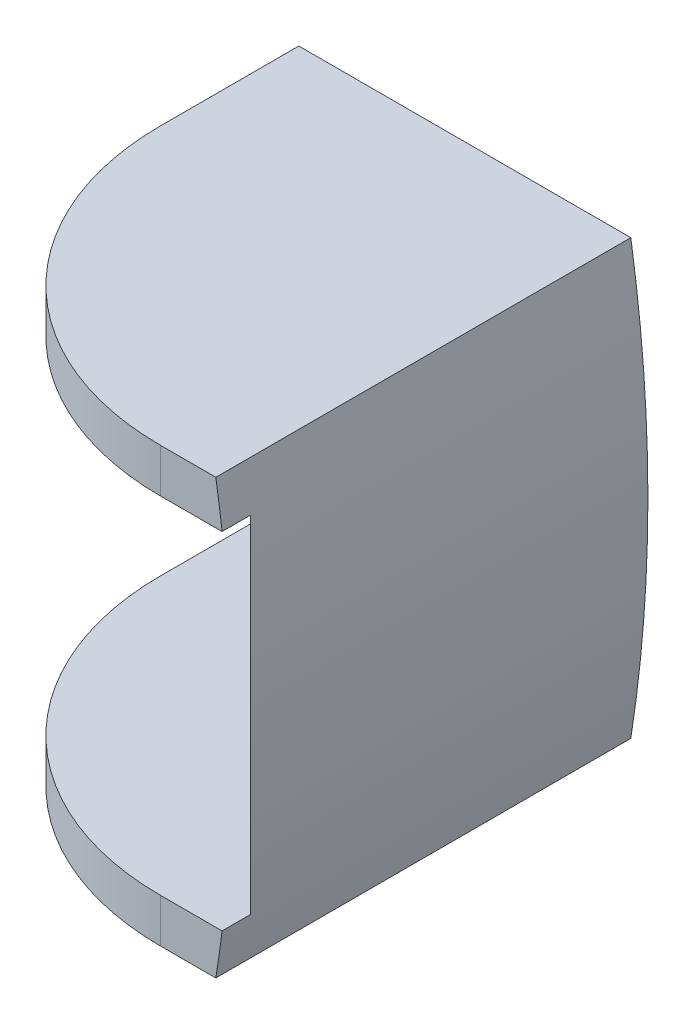
SolidWorks part; units mm, degrees
ref_plane "Front Plane" through (0, 0, 0) normal (0, 0, 1) x (1, 0, 0)
ref_plane "Top Plane" through (0, 0, 0) normal (0, 1, 0) x (1, 0, 0)
ref_plane "Right Plane" through (0, 0, 0) normal (1, 0, 0) x (0, 0, -1)
sketch "Sketch6" plane through (0, 0, 0) normal (0, 1, 0) x (1, 0, 0)
  line L1 (-12, 15) -> (12, 15)
  line L2 (-12, 15) -> (-12, -15)
  line L3 (-12, -15) -> (12, -15)
  line L4 (12, 15) -> (12, -15)
  line L5 (-12, 15) -> (12, -15) construction
  line L6 (-12, -15) -> (12, 15) construction
  point P0 (0, 0)
  dimension "D1" = 24
  dimension "D2" = 30
extrude "Boss-Extrude5" add sketch "Sketch6" along normal blind 31.35
sketch "Sketch10" plane through (0, 0, -15) normal (0, 0, -1) x (-1, 0, 0)
  line L0 (-12, 0) -> (-12, 31.35)
  arc A1 (-12, 0) -> (-12, 31.35) centre (86.7638, 15.675) cw
  dimension "D1" = 100
extrude "Boss-Extrude6" add sketch "Sketch10" against normal up to surface (30 mm away) up to face at (0, 15.675, 15)
ref_plane "Plane1" through (0, 15.675, 0) normal (0, 1, 0) x (1, 0, 0)
sketch "Sketch8" plane through (0, 15.675, 0) normal (0, 1, 0) x (1, 0, 0)
  line L0 (-12, 11.5) -> (-12, -15)
  line L1 (-12, 15) -> (-12, -15) construction
  line L4 (14.5, -15) -> (-12, 11.5)
  line L5 (12, 15) -> (-12, 15) construction
  line L6 (-12, -15) -> (14.5, -15)
  line L7 (-12, -15) -> (12, -15) construction
  dimension "D1" = 3.5
  dimension "D2" = 45
extrude "Cut-Extrude1" cut sketch "Sketch8" against normal offset from surface (12.5 mm away) 3.175 up to face at (0, 0, 0)
mirror "Mirror2" about plane through (0, 15.675, 0) normal (0, 1, 0) of "Cut-Extrude1"
fillet "Fillet1" radius 20 2 edges at (-12, 1.5875, 15) (-12, 29.7625, 15)
sketch "Sketch9" plane through (0, 0, -15) normal (0, 0, -1) x (-1, 0, 0)
  line L0 (12, 15.675) -> (-13.2362, 15.675) construction
  line L3 (12, 31.35) -> (12, 0) construction
  circle A0 centre (2.7638, 15.675) radius 2.15
  circle A1 centre (-7.2362, 15.675) radius 2.15
  arc A3 (-12, 31.35) -> (-12, 0) centre (86.7638, 15.675) ccw construction
  point P11 (0, 0)
  point P12 (0, 0)
  dimension "D1" = 4.3
  dimension "D2" = 10
  dimension "D3" = 6
extrude "Cut-Extrude2" cut sketch "Sketch9" against normal blind 8
sketch "Sketch11" plane through (-0.25, 0, 0.25) normal (-0.7071, 0, 0.7071) x (0.7071, 0, 0.7071)
  line L0 (-16.617, 15.675) -> (19.5587, 15.675) construction
  line L1 (-16.617, 3.175) -> (-16.617, 28.175) construction
  circle A0 centre (-1.6091, 4.825) radius 1.65
  circle A1 centre (4.7409, 4.825) radius 1.65
  circle A2 centre (4.7409, 26.525) radius 1.65
  circle A3 centre (-1.6091, 26.525) radius 1.65
  dimension "D1" = 3.3
extrude "Cut-Extrude3" cut sketch "Sketch11" against normal blind 9
